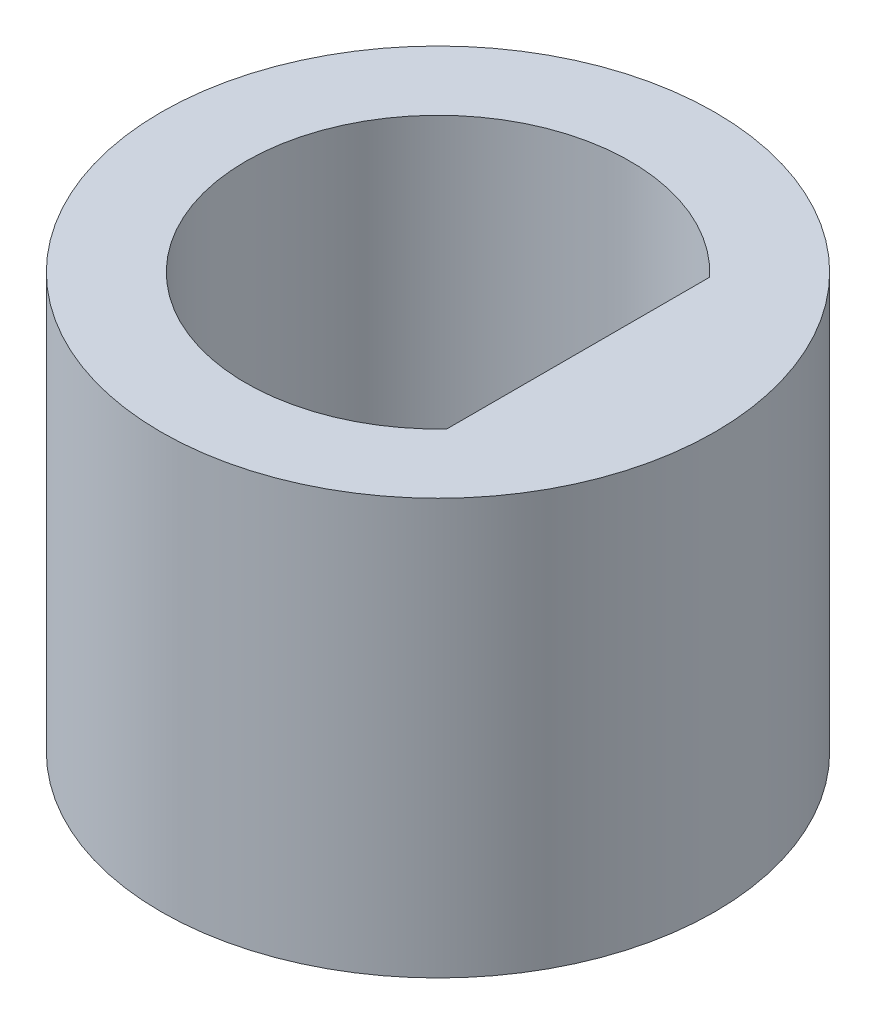
SolidWorks part; units mm, degrees
ref_plane "Front Plane" through (0, 0, 0) normal (0, 0, 1) x (1, 0, 0)
ref_plane "Top Plane" through (0, 0, 0) normal (0, 1, 0) x (1, 0, 0)
ref_plane "Right Plane" through (0, 0, 0) normal (1, 0, 0) x (0, 0, -1)
sketch "Sketch1" plane through (0, 0, 0) normal (0, 1, 0) x (1, 0, 0)
  line L1 (4.05, 0) -> (4.05, 3.7947)
  line L2 (4.05, 0) -> (4.05, -3.7947)
  arc A0 (4.05, 3.7947) -> (4.05, -3.7947) centre (0, 0) ccw
  circle A1 centre (0, 0) radius 8
  dimension "D1" = 11.1
  dimension "D2" = 16
extrude "Boss-Extrude1" add sketch "Sketch1" along normal blind 12
